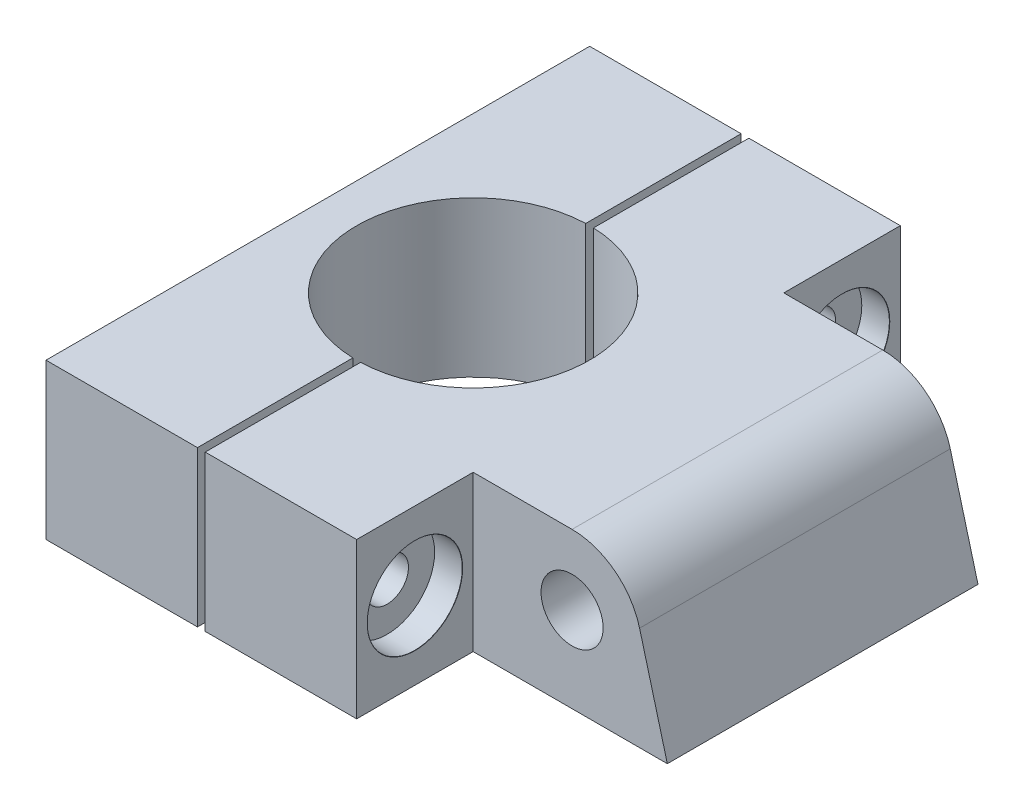
SolidWorks part; units mm, degrees
material "6061 Alloy"
ref_plane "Спереди" through (0, 0, 0) normal (0, 0, 1) x (1, 0, 0)
ref_plane "Сверху" through (0, 0, 0) normal (0, 1, 0) x (1, 0, 0)
ref_plane "Справа" through (0, 0, 0) normal (1, 0, 0) x (0, 0, -1)
other "Configuration Table"
sketch "Sketch1" plane through (0, 0, 0) normal (0, 0, 1) x (1, 0, 0)
  line L6 (20, -10) -> (45, -10)
  line L7 (-20, -10) -> (20, -10)
  line L8 (-20, -10) -> (-20, 10)
  line L9 (-20, 10) -> (20, 10)
  line L10 (20, -10) -> (20, 10)
  line L11 (-20, -10) -> (20, 10) construction
  line L12 (-20, 10) -> (20, -10) construction
  line L13 (45, -10) -> (41.4284, 3.3294)
  line L14 (32.7351, 10) -> (20, 10)
  arc A1 (41.4284, 3.3294) -> (32.7351, 10) centre (32.7351, 1) ccw
  circle A2 centre (32.7351, 1) radius 4
  point P0 (0, 0)
  point P9 (0, 0)
  dimension "D3" = 8
  dimension "D5" = 9
  dimension "D1" = 20
  dimension "D2" = 75
  dimension "D4" = 25
  dimension "D7" = 40
extrude "Boss-Extrude2" add sketch "Sketch1" along normal mid plane 70 contours L7 L10 L9 L8 region at (0, 0, 0)
extrude "Boss-Extrude3" add sketch "Sketch1<3>" along normal mid plane 40 contours L13 A1 L14 L10 L6 A2 region at (20.3202, 0, 0)
sketch "Sketch1<3>" plane through (0, 0, 0) normal (0, 0, 1) x (1, 0, 0) same geometry as "Sketch1"
sketch "Sketch2" plane through (0, 10, 0) normal (0, 1, 0) x (1, 0, 0)
  line L0 (-20, 35) -> (20, 35) construction
  line L1 (-0.5, 35) -> (0.5, 35)
  line L2 (-0.5, 35) -> (-0.5, -35)
  line L3 (-0.5, -35) -> (0.5, -35)
  line L4 (0.5, 35) -> (0.5, -35)
  line L5 (-20, -35) -> (20, -35) construction
  line L6 (0, 8.562) -> (0, -10.7167) construction
  circle A0 centre (0, 0) radius 15
  dimension "D1" = 30
  dimension "D2" = 1
extrude "Cut-Extrude1" cut sketch "Sketch2" against normal through all contours L2 A0 | L4 A0 | L4 L3 L2 L1 region at (-6.6372, 10, 0) region at (6.6372, 10, 0)
sketch "Sketch6" plane through (20, 0, 0) normal (1, 0, 0) x (0, 0, -1)
  line L0 (-27.5, 0) -> (27.5, 0) construction
  line L1 (0, 16.8324) -> (0, -20.6297) construction
  line L2 (-27.5, 6.5358) -> (-27.5, -7.4121) construction
  line L3 (-20, -10) -> (-20, 10) construction
  line L4 (-35, -10) -> (-35, 10) construction
hole_wizard "CBORE for M5 Hex Head Bolt1" positions "Sketch7" profile "Sketch8" counterbore size "M5" standard "ANSI Metric" end condition through all
sketch "Sketch7" plane through (20, 0, 0) normal (1, 0, 0) x (0, 0, -1)
  point P0 (-27.5, 0)
  point P3 (27.5, 0)
sketch "Sketch8" plane through (20, 0, 27.5) normal (0, 1, 0) x (0, 0, -1)
  line L0 (0, 0) -> (0, 40)
  line L1 (0, 40) -> (2.75, 40)
  line L3 (2.75, 40) -> (2.75, 3.58)
  line L4 (6.12, 3.58) -> (2.75, 3.58)
  line L5 (6.12, 3.58) -> (6.12, 0.025)
  line L6 (6.12, 0.025) -> (6.145, 0)
  line L7 (6.145, 0) -> (0, 0)
  line L8 (-6.12, 0.025) -> (-6.145, 0) construction
  line L11 (0, -6.35) -> (0, 107.95) construction
  dimension "Thru Hole Dia." = 5.5
  dimension "Thru Hole Depth" = 40
  dimension "C'Bore Dia." = 12.24
  dimension "C'Bore Depth" = 3.58
  dimension "Near C'Sink Dia." = 12.29
  dimension "Near C'Sink Angle" = 90
